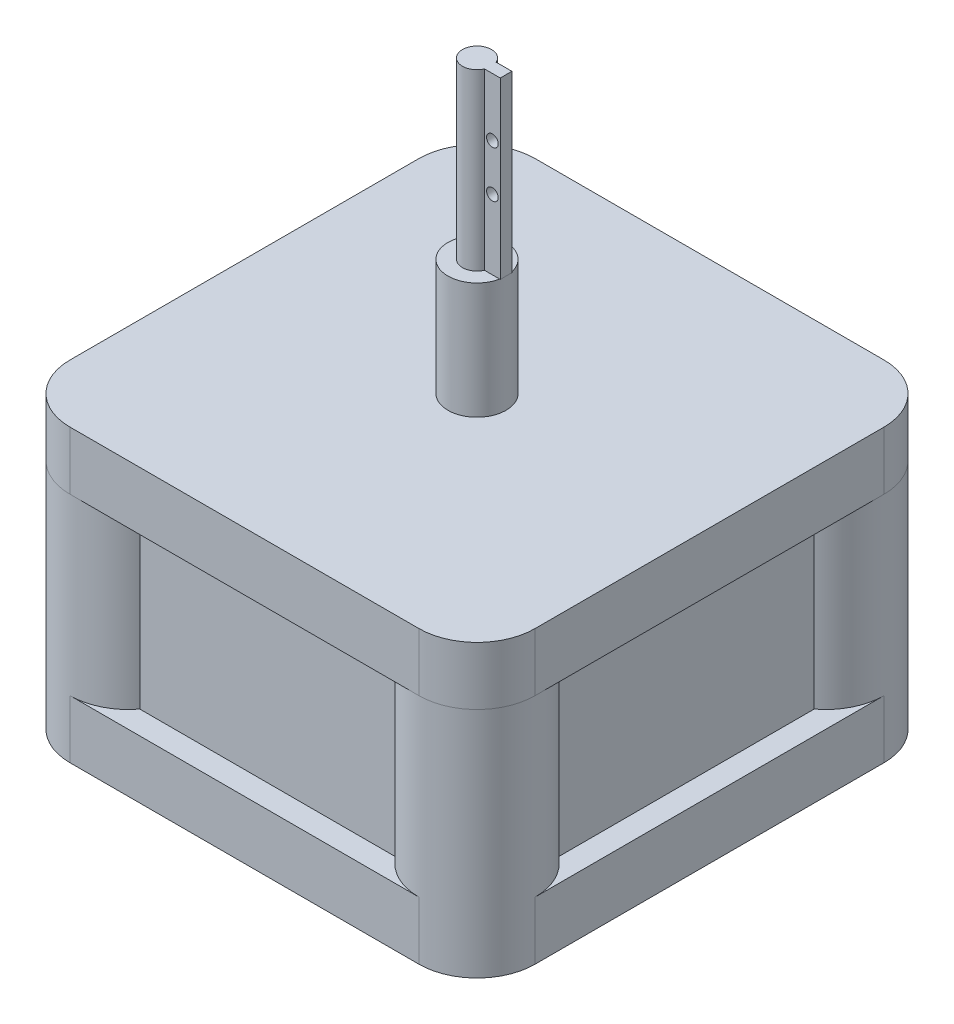
SolidWorks part; units mm, degrees
ref_plane "Front Plane" through (0, 0, 0) normal (0, 0, 1) x (1, 0, 0)
ref_plane "Top Plane" through (0, 0, 0) normal (0, 1, 0) x (1, 0, 0)
ref_plane "Right Plane" through (0, 0, 0) normal (1, 0, 0) x (0, 0, -1)
sketch "Sketch1" plane through (0, 0, 0) normal (0, 1, 0) x (1, 0, 0)
  line L1 (0, 0) -> (50.8, 0)
  line L2 (0, 0) -> (0, 50.8)
  line L3 (0, 50.8) -> (50.8, 50.8)
  line L4 (50.8, 0) -> (50.8, 50.8)
  dimension "D1" = 50.8
  dimension "D2" = 50.8
extrude "Boss-Extrude1" add sketch "Sketch1" along normal blind 6.35
fillet "Fillet1" radius 6.35 4 edges at (0, 3.175, -50.8) (50.8, 3.175, -50.8) (50.8, 3.175, 0) (0, 3.175, 0)
sketch "Sketch3" plane through (0, 6.35, 0) normal (0, 1, 0) x (1, 0, 0)
  line L0 (0, 44.45) -> (0, 6.35) construction
  line L1 (11.43, 48.26) -> (39.37, 48.26)
  line L2 (2.54, 39.37) -> (2.54, 11.43)
  line L3 (11.43, 2.54) -> (39.37, 2.54)
  line L4 (48.26, 39.37) -> (48.26, 11.43)
  line L5 (6.35, 0) -> (44.45, 0) construction
  arc A4 (11.43, 48.26) -> (2.54, 39.37) centre (6.35, 44.45) ccw
  arc A5 (48.26, 39.37) -> (39.37, 48.26) centre (44.45, 44.45) ccw
  arc A6 (2.54, 11.43) -> (11.43, 2.54) centre (6.35, 6.35) ccw
  arc A7 (39.37, 2.54) -> (48.26, 11.43) centre (44.45, 6.35) ccw
  dimension "D5" = 12.7
  dimension "D10" = 12.7
  dimension "D11" = 12.7
  dimension "D12" = 12.7
  dimension "D2" = 27.94
  dimension "D3" = 2.54
  dimension "D4" = 2.54
  dimension "D6" = 3.81
  dimension "D7" = 3.81
  dimension "D8" = 3.81
  dimension "D9" = 3.81
  dimension "D13" = 3.81
  dimension "D14" = 3.81
  dimension "D15" = 3.81
  dimension "D16" = 3.81
  dimension "D17" = 27.94
extrude "Boss-Extrude2" add sketch "Sketch3" along normal blind 19.05
sketch "Sketch5" plane through (0, 25.4, 0) normal (0, 1, 0) x (1, 0, 0)
  line L0 (2.54, 39.37) -> (2.54, 11.43) construction
  line L1 (0, 50.8) -> (50.8, 50.8)
  line L2 (0, 50.8) -> (0, 0)
  line L3 (0, 0) -> (50.8, 0)
  line L4 (50.8, 50.8) -> (50.8, 0)
  line L5 (11.43, 2.54) -> (39.37, 2.54) construction
  dimension "D1" = 50.8
  dimension "D2" = 50.8
  dimension "D3" = 2.54
  dimension "D4" = 2.54
extrude "Boss-Extrude3" add sketch "Sketch5" along normal blind 6.35
fillet "Fillet2" radius 6.35 4 edges at (50.8, 28.575, -50.8) (0, 28.575, -50.8) (50.8, 28.575, 0) (0, 28.575, 0)
sketch "Sketch6" plane through (0, 31.75, 0) normal (0, 1, 0) x (1, 0, 0)
  line L0 (6.35, 0) -> (44.45, 0) construction
  line L1 (0, 44.45) -> (0, 6.35) construction
  circle A0 centre (25.4, 25.4) radius 3.175
  dimension "D3" = 6.35
  dimension "D1" = 25.4
  dimension "D2" = 25.4
extrude "Boss-Extrude4" add sketch "Sketch6" along normal blind 12.7
sketch "Sketch7" plane through (0, 44.45, 0) normal (0, 1, 0) x (1, 0, 0)
  line L0 (28.575, 26.035) -> (28.575, 24.765)
  line L1 (28.575, 24.765) -> (26.855, 24.765)
  line L2 (28.575, 26.035) -> (26.855, 26.035)
  arc A0 (26.855, 26.035) -> (26.855, 24.765) centre (25.4, 25.4) ccw
  dimension "D1" = 3.175
  dimension "D2" = 1.27
  dimension "D3" = 0.635
  dimension "D4" = 3.175
extrude "Boss-Extrude5" add sketch "Sketch7" along normal blind 19.05
sketch "Sketch8" plane through (0, 0, -24.765) normal (0, 0, 1) x (1, 0, 0)
  line L0 (28.575, 63.5) -> (28.575, 44.45) construction
  line L1 (26.855, 44.45) -> (28.5109, 44.45) construction
  circle A0 centre (27.7156, 52.07) radius 0.635
  circle A1 centre (27.7156, 57.15) radius 0.635
  dimension "D1" = 1.27
  dimension "D2" = 0.8594
  dimension "D3" = 7.62
  dimension "D4" = 2
extrude "Cut-Extrude2" cut sketch "Sketch8" against normal blind 2.54
